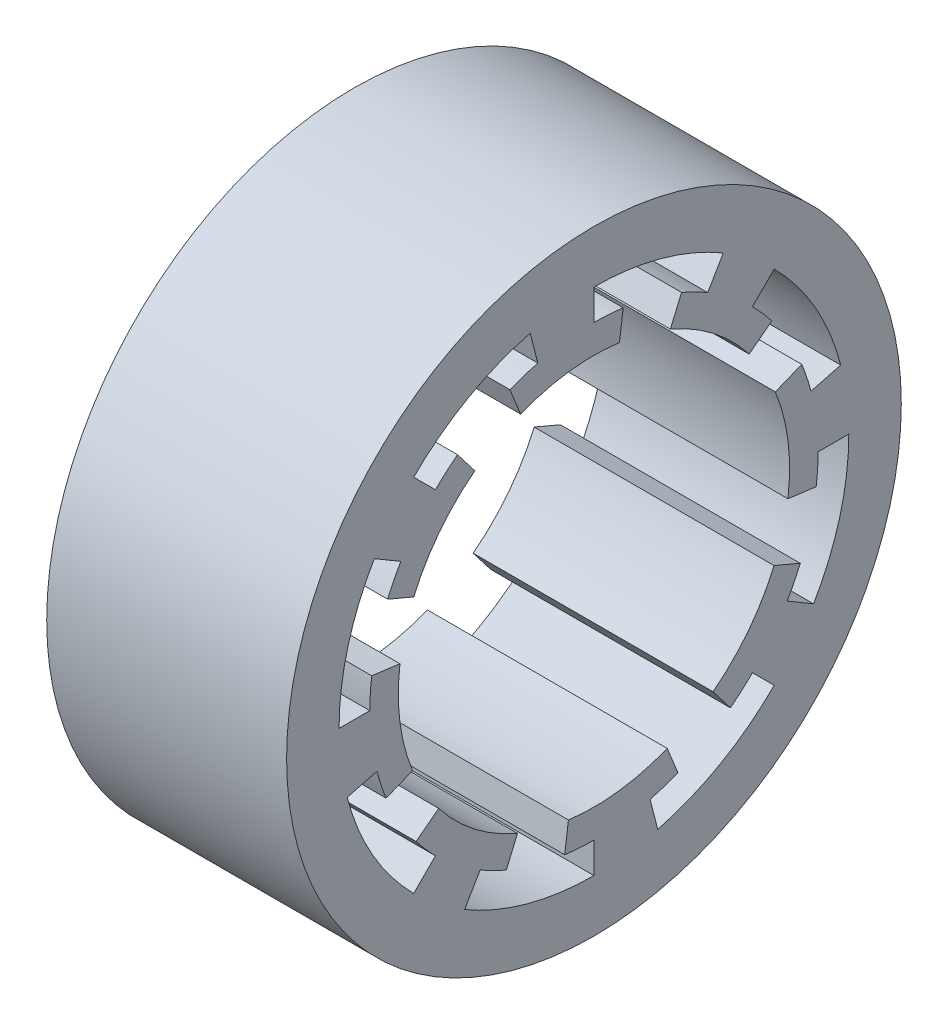
SolidWorks part; units mm, degrees
material "TPU 95A"
ref_plane "Front Plane" through (0, 0, 0) normal (1, 0, 0) x (0, 1, 0)
ref_plane "Top Plane" through (0, 0, 0) normal (0, 0, 1) x (0, 1, 0)
ref_plane "Right Plane" through (0, 0, 0) normal (0, 1, 0) x (-1, 0, 0)
sketch "Sketch1" plane through (0, 0, 0) normal (1, 0, 0) x (0, 1, 0)
  circle A0 centre (0, 0) radius 26.035
  circle A1 centre (0, 0) radius 21.59
  dimension "D1" = 52.07
  dimension "D2" = 43.18
extrude "Boss-Extrude1" add sketch "Sketch1" along normal blind 20.32
sketch "Sketch3" plane through (0, 0, 0) normal (1, 0, 0) x (0, 1, 0)
  line L0 (0, 0) -> (0, 21.59) construction
  line L1 (0, 0) -> (-5.4057, 20.9023) construction
  line L2 (0, 0) -> (-10.6314, 18.791) construction
  line L3 (0, 0) -> (5.5879, 20.8543) construction
  line L4 (-5.4057, 20.9023) -> (-4.7538, 18.3817)
  line L5 (0, 0) -> (-7.1125, 17.604) construction
  line L6 (0, 0) -> (2.4782, 18.8241) construction
  line L7 (0, 21.59) -> (0, 18.9865)
  line L8 (-7.1125, 17.604) -> (-6.2085, 15.3667)
  line L9 (2.4782, 18.8241) -> (2.1633, 16.4317)
  circle A0 centre (0, 0) radius 21.59 construction
  circle A1 centre (0, 0) radius 18.9865 construction
  circle A3 centre (0, 0) radius 16.5735 construction
  arc A4 (-4.7538, 18.3817) -> (-7.1125, 17.604) centre (0, 0) ccw
  arc A5 (0, 18.9865) -> (2.4782, 18.8241) centre (0, 0) cw
  arc A6 (-6.2085, 15.3667) -> (2.1633, 16.4317) centre (0, 0) cw
  arc A7 (-5.4057, 20.9023) -> (0, 21.59) centre (0, 0) cw
  dimension "D6" = 43.18
  dimension "D7" = 37.973
  dimension "D8" = 33.147
  dimension "D1" = 14.5
  dimension "D2" = 15
  dimension "D3" = 15
  dimension "D4" = 7.5
  dimension "D5" = 7.5
extrude "Boss-Extrude2" add sketch "Sketch3" along normal up to surface (20.32 mm away) up to face at (20.32, 0, -26.035)
sketch "Sketch4" plane through (0, 0, 0) normal (0, 0, 1) x (0, 1, 0)
  line L0 (0, 0) -> (0, -7.3257) construction
  line L1 (26.035, 0) -> (-26.035, 0) construction
pattern_circular "CirPattern1" count 8 every 45 about axis through (0, 0, 0) along (1, 0, 0) of "Boss-Extrude2"
